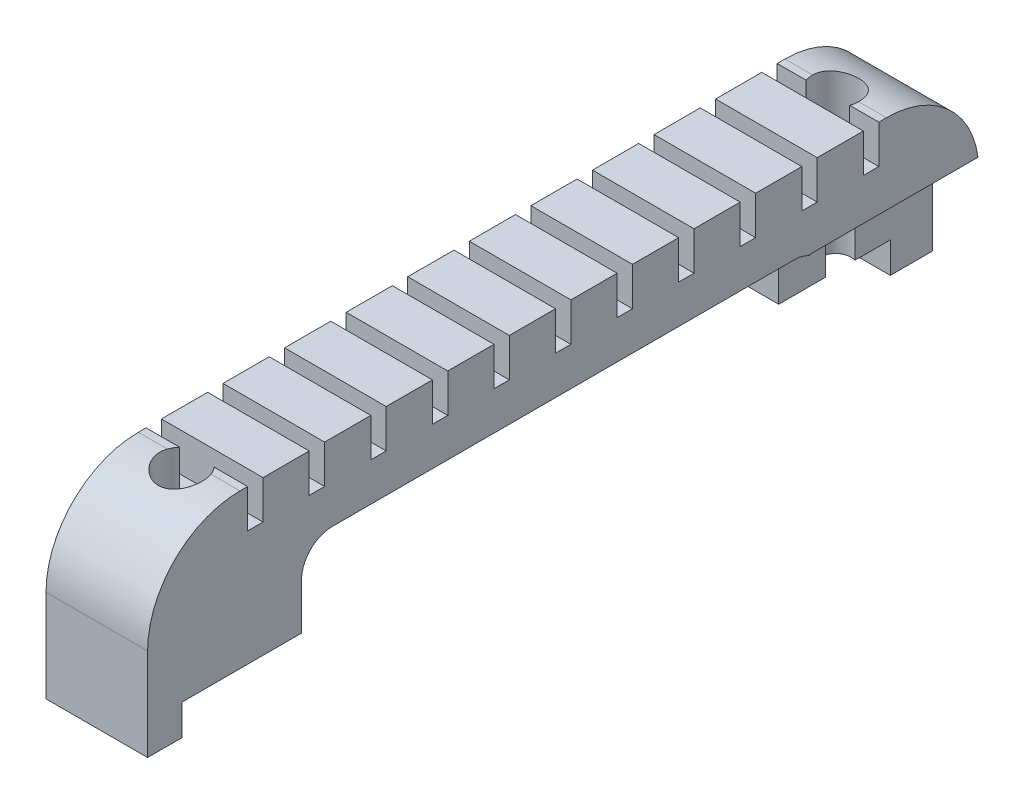
SolidWorks part; units mm, degrees
ref_plane "前视基准面" through (0, 0, 0) normal (0, 0, 1) x (1, 0, 0)
ref_plane "上视基准面" through (0, 0, 0) normal (0, 1, 0) x (1, 0, 0)
ref_plane "右视基准面" through (0, 0, 0) normal (1, 0, 0) x (0, 0, -1)
other "Configuration Table"
sketch "草图1" plane through (0, 0, 0) normal (0, 1, 0) x (1, 0, 0)
  line L0 (-40, 24) -> (40, 24) construction
  line L1 (-40, 24) -> (-40, -24) construction
  line L2 (-40, -24) -> (40, -24) construction
  line L3 (40, 24) -> (40, -24) construction
  line L4 (-40, 24) -> (40, -24) construction
  line L5 (-40, -24) -> (40, 24) construction
  line L6 (-34, 18) -> (34, 18) construction
  line L7 (-34, 18) -> (-34, -18) construction
  line L8 (-34, -18) -> (34, -18) construction
  line L9 (34, 18) -> (34, -18) construction
  line L10 (-34, 18) -> (34, -18) construction
  line L11 (-34, -18) -> (34, 18) construction
  line L13 (-28.3, 27) -> (-21.7, 27)
  line L14 (-28.3, 27) -> (-28.3, -27)
  line L15 (-28.3, -27) -> (-21.7, -27)
  line L16 (-21.7, 27) -> (-21.7, -27)
  line L17 (-28.3, 27) -> (-21.7, -27) construction
  line L18 (-28.3, -27) -> (-21.7, 27) construction
  circle A0 centre (25, -21.5) radius 1.5 construction
  circle A1 centre (25, 21) radius 1.5 construction
  circle A2 centre (0, 21) radius 1.5 construction
  circle A3 centre (0, -21.5) radius 1.5 construction
  circle A4 centre (-25, -21.5) radius 1.5
  circle A5 centre (-25, 21) radius 1.5
  point P0 (0, 0)
  point P17 (0, 0)
  point P22 (-25, 0)
  dimension "D1" = 48
  dimension "D2" = 36
  dimension "D3" = 68
  dimension "D4" = 6.6
  dimension "D5" = 25
  dimension "D6" = 54
extrude "凸台-拉伸1" add sketch "草图1" along normal blind 12
fillet "圆角1" radius 6 2 edges at (-25, 12, -27) (-25, 12, 27)
sketch "草图2" plane through (-28.3, 0, 0) normal (-1, 0, 0) x (0, 0, 1)
  line L1 (-17, 7) -> (17, 7)
  line L2 (-17, 7) -> (-17, -7)
  line L3 (-17, -7) -> (17, -7)
  line L4 (17, 7) -> (17, -7)
  line L5 (-17, 7) -> (17, -7) construction
  line L6 (-17, -7) -> (17, 7) construction
  point P0 (0, 0)
  dimension "D1" = 14
  dimension "D2" = 34
extrude "切除-拉伸1" cut sketch "草图2" against normal blind 20
fillet "圆角2" radius 2 2 edges at (-25, 7, 17) (-25, 7, -17)
sketch "草图3" plane through (-28.3, 0, 0) normal (-1, 0, 0) x (0, 0, 1)
  line L0 (-21, 12) -> (21, 12) construction
  line L1 (-0.5, 9.5) -> (0.5, 9.5)
  line L2 (-0.5, 9.5) -> (-0.5, 12)
  line L3 (-0.5, 12) -> (0.5, 12)
  line L4 (0.5, 9.5) -> (0.5, 12)
  line L5 (-0.5, 9.5) -> (0.5, 12) construction
  line L6 (-0.5, 12) -> (0.5, 9.5) construction
  line L7 (3.5, 9.5) -> (3.5, 12)
  line L8 (3.5, 12) -> (4.5, 12)
  line L9 (4.5, 9.5) -> (4.5, 12)
  line L10 (3.5, 9.5) -> (4.5, 9.5)
  line L11 (7.5, 9.5) -> (7.5, 12)
  line L12 (7.5, 12) -> (8.5, 12)
  line L13 (8.5, 9.5) -> (8.5, 12)
  line L14 (7.5, 9.5) -> (8.5, 9.5)
  line L15 (11.5, 9.5) -> (11.5, 12)
  line L16 (11.5, 12) -> (12.5, 12)
  line L17 (12.5, 9.5) -> (12.5, 12)
  line L18 (11.5, 9.5) -> (12.5, 9.5)
  line L19 (15.5, 9.5) -> (15.5, 12)
  line L20 (15.5, 12) -> (16.5, 12)
  line L21 (16.5, 9.5) -> (16.5, 12)
  line L22 (15.5, 9.5) -> (16.5, 9.5)
  line L23 (19.5, 9.5) -> (19.5, 12)
  line L24 (19.5, 12) -> (20.5, 12)
  line L25 (20.5, 9.5) -> (20.5, 12)
  line L26 (19.5, 9.5) -> (20.5, 9.5)
  line L27 (-4.5, 9.5) -> (-3.5, 9.5)
  line L28 (-4.5, 9.5) -> (-4.5, 12)
  line L29 (-4.5, 12) -> (-3.5, 12)
  line L30 (-3.5, 9.5) -> (-3.5, 12)
  line L31 (-4.5, 9.5) -> (-3.5, 12) construction
  line L32 (-4.5, 12) -> (-3.5, 9.5) construction
  line L33 (-8.5, 9.5) -> (-7.5, 9.5)
  line L34 (-8.5, 9.5) -> (-8.5, 12)
  line L35 (-8.5, 12) -> (-7.5, 12)
  line L36 (-7.5, 9.5) -> (-7.5, 12)
  line L37 (-8.5, 9.5) -> (-7.5, 12) construction
  line L38 (-8.5, 12) -> (-7.5, 9.5) construction
  line L39 (-12.5, 9.5) -> (-11.5, 9.5)
  line L40 (-12.5, 9.5) -> (-12.5, 12)
  line L41 (-12.5, 12) -> (-11.5, 12)
  line L42 (-11.5, 9.5) -> (-11.5, 12)
  line L43 (-12.5, 9.5) -> (-11.5, 12) construction
  line L44 (-12.5, 12) -> (-11.5, 9.5) construction
  line L45 (-16.5, 9.5) -> (-15.5, 9.5)
  line L46 (-16.5, 9.5) -> (-16.5, 12)
  line L47 (-16.5, 12) -> (-15.5, 12)
  line L48 (-15.5, 9.5) -> (-15.5, 12)
  line L49 (-16.5, 9.5) -> (-15.5, 12) construction
  line L50 (-16.5, 12) -> (-15.5, 9.5) construction
  line L51 (-20.5, 9.5) -> (-19.5, 9.5)
  line L52 (-20.5, 9.5) -> (-20.5, 12)
  line L53 (-20.5, 12) -> (-19.5, 12)
  line L54 (-19.5, 9.5) -> (-19.5, 12)
  line L55 (-20.5, 9.5) -> (-19.5, 12) construction
  line L56 (-20.5, 12) -> (-19.5, 9.5) construction
  point P0 (0, 10.75)
  point P30 (-4, 10.75)
  point P35 (-8, 10.75)
  point P40 (-12, 10.75)
  point P45 (-16, 10.75)
  point P50 (-20, 10.75)
  dimension "D1" = 1
  dimension "D2" = 2.5
extrude "切除-拉伸2" cut sketch "草图3" against normal through all
sketch "草图4" plane through (0, 0, 0) normal (0, -1, 0) x (1, 0, 0)
  line L0 (-25, 21.5) -> (-25, -21) construction
  line L2 (-32.2789, 24.75) -> (-17.7211, 24.75)
  line L3 (-32.2789, 24.75) -> (-32.2789, -24.25)
  line L4 (-32.2789, -24.25) -> (-17.7211, -24.25)
  line L5 (-17.7211, 24.75) -> (-17.7211, -24.25)
  line L6 (-32.2789, 24.75) -> (-17.7211, -24.25) construction
  line L7 (-32.2789, -24.25) -> (-17.7211, 24.75) construction
  point P4 (-25, 0.25)
  dimension "D1" = 49
extrude "切除-拉伸3" cut sketch "草图4" against normal blind 2
sketch "草图6" plane through (0, 2, 0) normal (0, -1, 0) x (1, 0, 0)
  circle A0 centre (-25, 21.5) radius 1.5
  circle A1 centre (-25, 21.5) radius 1
  circle A5 centre (-25, -21) radius 1
  circle A6 centre (-25, -21) radius 1.5
  dimension "D1" = 2
  dimension "D2" = 3
  dimension "D3" = 3
  dimension "D4" = 2
extrude "凸台-拉伸2" add sketch "草图6" against normal blind 4
sketch "草图7" plane through (0, 0, 0) normal (0, -1, 0) x (1, 0, 0)
  line L10 (-24.7, -16) -> (-18.7, -16)
  line L11 (-24.7, -16) -> (-24.7, -38)
  line L12 (-24.7, -38) -> (-18.7, -38)
  line L13 (-18.7, -16) -> (-18.7, -38)
  line L14 (-24.7, -16) -> (-18.7, -38) construction
  line L15 (-24.7, -38) -> (-18.7, -16) construction
  point P0 (-21.7, -27)
  dimension "D1" = 22
  dimension "D2" = 6
extrude "切除-拉伸4" cut sketch "草图7" against normal blind 6.8
